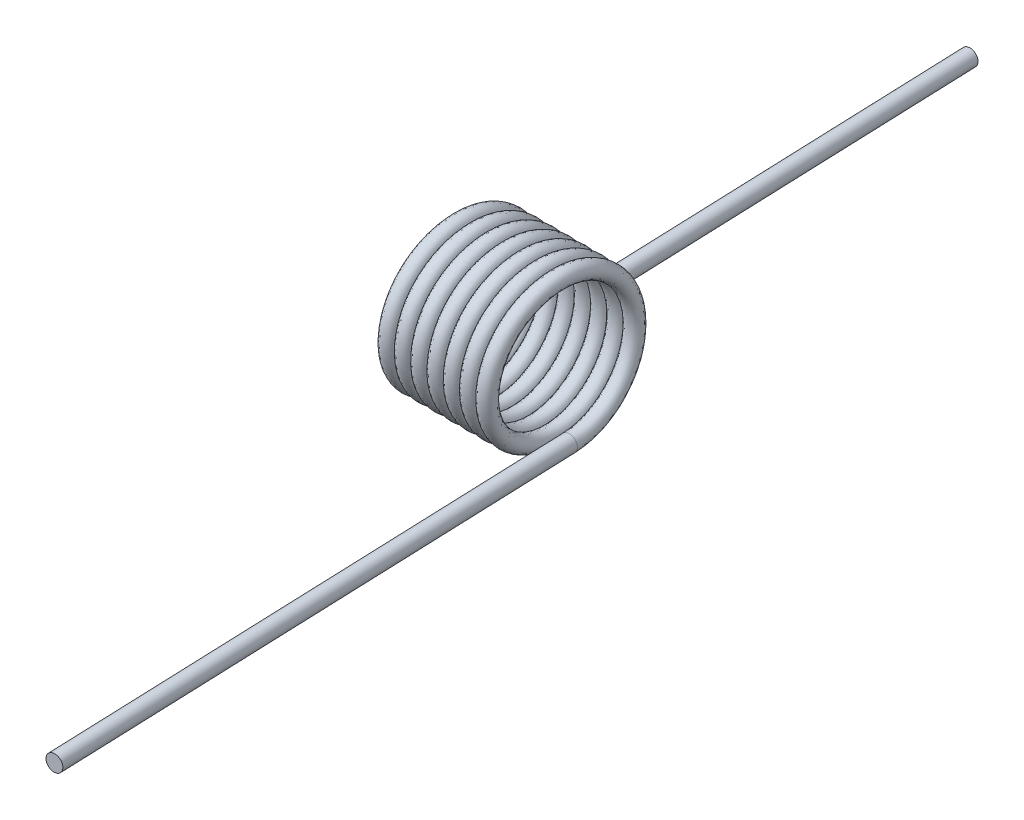
SolidWorks part; units mm, degrees
material "Alloy Steel"
ref_plane "Front" through (0, 0, 0) normal (0, 0, 1) x (1, 0, 0)
ref_plane "Top" through (0, 0, 0) normal (0, 1, 0) x (1, 0, 0)
ref_plane "Right" through (0, 0, 0) normal (1, 0, 0) x (0, 0, -1)
sketch "Sketch1" plane through (0, 0, 0) normal (1, 0, 0) x (0, 0, -1)
  line L0 (0, -3.6449) -> (0, -4.6101) construction
  line L1 (0, -4.6101) -> (31.75, -4.6101) construction
  line L2 (0, -4.6101) -> (-31.75, -4.6101) construction
  line L3 (0, 0) -> (4.6101, 0) construction
  line L4 (0, 0) -> (0, -4.6101) construction
  line L5 (-31.75, -4.6101) -> (-31.75, -3.6449) construction
  line L6 (-31.75, -3.6449) -> (0, -3.6449) construction
  line L7 (31.75, -4.6101) -> (31.75, -3.6449) construction
  line L8 (31.75, -3.6449) -> (0, -3.6449) construction
  circle A0 centre (0, 0) radius 4.6101 construction
  circle A1 centre (0, 0) radius 3.048 construction
  circle A2 centre (0, 0) radius 4.1275 construction
  point P7 (0, -4.1275)
  point P10 (0, 4.6101)
  dimension "OD" = 9.2202
  dimension "For Shaft Diameter" = 6.096
  dimension "Wire Diameter" = 0.9652
  dimension "Leg Length" = 31.75
  dimension "Deflection Angle" = 180
sketch "Sketch2" plane through (0, 0, 0) normal (1, 0, 0) x (0, 0, -1)
  circle A0 centre (0, 0) radius 4.1275 construction
  circle A2 centre (0, 0) radius 4.1275
curve "Helix/Spiral1" pitch 0.9662 height 6.7634 radius 4.1275 left hand yes centre (0, 0, 0) axis (-1, 0, 0) start towards (0, 0, -1)
ref_plane "Plane1" through (0, -4.1275, 0) normal (-0.0372, 0, -0.9993) x (0.999, -0.0232, -0.0372)
sketch "Sketch3" plane through (0, -4.1275, 0) normal (-0.0372, 0, -0.9993) x (0.999, -0.0232, -0.0372)
  circle A0 centre (0, 0) radius 0.4826
  dimension "D1" = 0.9652
sweep "Sweep1" add profiles "Sketch3" path "Helix/Spiral1"
sketch "Sketch4" plane through (0, 0, 0) normal (0.0372, 0, 0.9993) x (-0.999, 0.0232, 0.0372)
  circle A1 centre (-0.0959, 4.1264) radius 0.4826
  circle A2 centre (-0.0959, 4.1264) radius 0.4826
  dimension "D1" = 0
extrude "Extrude1" add sketch "Sketch4" along normal blind 31.75
sketch "Sketch5" plane through (-0.0094, 0, -0.2516) normal (-0.0372, 0, -0.9993) x (0.9982, 0.048, -0.0372)
  circle A1 centre (-6.949, 3.7984) radius 0.4826
  circle A2 centre (-6.949, 3.7984) radius 0.4826
  dimension "D1" = 0
extrude "Extrude2" add sketch "Sketch5" along normal blind 31.75
sketch "Sketch6" plane through (0, 0, 0) normal (1, 0, 0) x (0, 0, -1)
  circle A2 centre (0, 0) radius 3.6449 construction
ref_plane "Plan1" through (-7, 0, 0) normal (1, 0, 0) x (0, 0, -1)
equation "\"D4@Helix/Spiral1\" = \"Wire Diameter@Sketch1\" + .001"
equation "\"D1@Sketch3\"=\"Wire Diameter@Sketch1\""
equation "\"D1@Extrude2\"=\"Leg Length@Sketch1\""
equation "\"Leg Length@Extrude1\"=\"Leg Length@Sketch1\""
